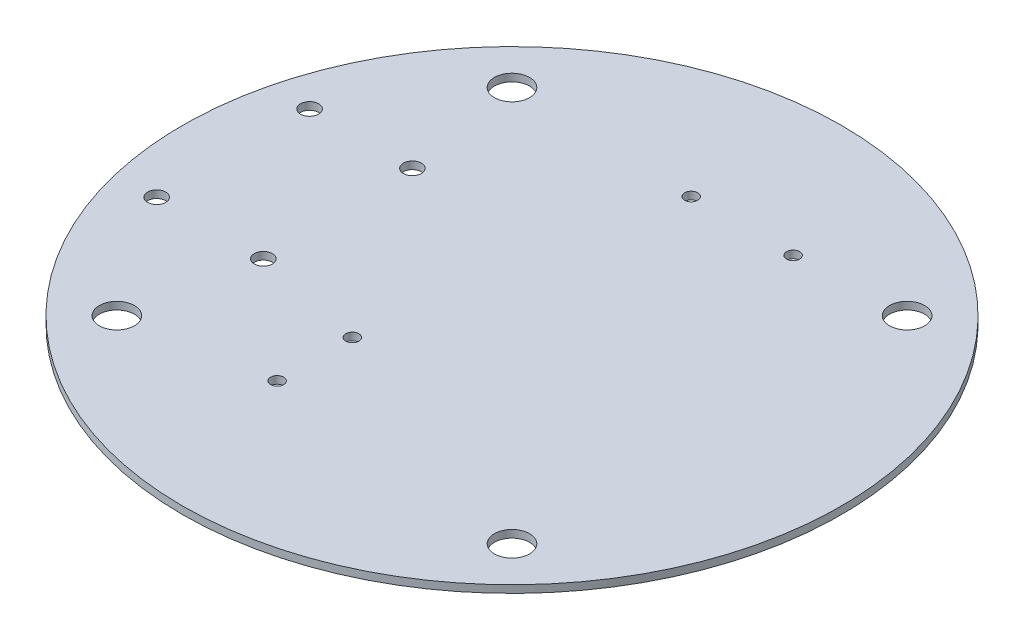
SolidWorks part; units mm, degrees
ref_plane "Front Plane" through (0, 0, 0) normal (0, 0, 1) x (1, 0, 0)
ref_plane "Top Plane" through (0, 0, 0) normal (0, 1, 0) x (1, 0, 0)
ref_plane "Right Plane" through (0, 0, 0) normal (1, 0, 0) x (0, 0, -1)
sketch "Sketch1" plane through (0, 0, 0) normal (0, 1, 0) x (1, 0, 0)
  circle A0 centre (0, 0) radius 65.7
  dimension "PCBdiam" = 131.4
extrude "Boss-Extrude1" add sketch "Sketch1" along normal blind 1.5
hole_wizard "M6 Clearance Hole1" positions "Sketch2" profile "Sketch4" hole size "M6" standard "ANSI Metric" end condition through all
sketch "Sketch2" plane through (0, 1.5, 0) normal (0, 1, 0) x (1, 0, 0)
  line L0 (0, 0) -> (-28.5457, 28.5457) construction
  line L1 (-39.3858, -39.3858) -> (0, 0) construction
  line L3 (0, 0) -> (-73.422, 0) construction
  circle A0 centre (0, 0) radius 65.7 construction
  ellipse E2 centre (-116.4291, -176.9435) end of major axis (-117.7556, -176.0714) minor radius 1.3748
  ellipse E3 centre (-116.4291, -176.9435) end of major axis (-115.1026, -177.8157) minor radius 1.3748
  point P7 (-39.3858, -39.3858)
  dimension "D1" = 0
  dimension "holeRadius" = 55.7
  dimension "D2" = 45
sketch "Sketch4" plane through (-39.3858, 1.5, 39.3858) normal (1, 0, 0) x (0, 0, 1)
  line L0 (0, 0) -> (0, 1.5)
  line L1 (0, 1.5) -> (3.5, 1.5)
  line L2 (3.5, 1.5) -> (3.5, 0)
  line L5 (3.5, 0) -> (0, 0)
  line L11 (0, -6.35) -> (0, 107.95) construction
  dimension "Thru Hole Dia." = 7
  dimension "Thru Hole Depth" = 1.5
pattern_circular "CirPattern1" count 4 over 360 about axis through (0, 1.5, 0) along (0, -1, 0) of "M6 Clearance Hole1"
sketch "Teensy Outline" plane through (0, 1.5, 0) normal (0, 1, 0) x (1, 0, 0)
  line L1 (-29.654, 50.7) -> (-12, 50.7)
  line L2 (-29.654, 50.7) -> (-29.654, -7.72)
  line L3 (-29.654, -7.72) -> (-12, -7.72)
  line L4 (-12, 50.7) -> (-12, -7.72)
  circle A1 centre (0, 0) radius 65.7 construction
  dimension "D1" = 17.654
  dimension "D2" = 58.42
  dimension "D3" = 12
  dimension "D4" = 15
sketch "BMP390 Outline" plane through (0, 1.5, 0) normal (0, 1, 0) x (1, 0, 0)
  line L0 (17.61, 54.7) -> (-5.25, 54.7) construction
  line L2 (20.15, 56.04) -> (-5.25, 56.04)
  line L3 (-5.25, 56.04) -> (-5.25, 38.26)
  line L4 (20.15, 38.26) -> (-5.25, 38.26)
  line L6 (20.15, 56.04) -> (20.15, 38.26)
  line L7 (17.61, 54.7) -> (17.61, 38.26) construction
  line L8 (-29.654, 50.7) -> (-12, 50.7) construction
  line L9 (-12, 50.7) -> (-12, -7.72) construction
  dimension "D1" = 17.78
  dimension "D2" = 25.4
  dimension "D3" = 1.34
  dimension "D4" = 4
  dimension "D5" = 6.75
  dimension "D6" = 5.08
sketch "NEO-6M Outline" plane through (0, 1.5, 0) normal (0, 1, 0) x (1, 0, 0)
  line L0 (-50.84, 17.78) -> (-50.84, 15.24) construction
  line L1 (-58.34, 17.78) -> (-32, 17.78)
  line L2 (-58.34, 17.78) -> (-58.34, -17.78)
  line L3 (-58.34, -17.78) -> (-32, -17.78)
  line L4 (-32, 17.78) -> (-32, -17.78)
  line L5 (-50.84, 15.24) -> (-39.5, 15.24) construction
  line L6 (-39.5, 15.24) -> (-39.5, 17.78) construction
  point P4 (-32, 0)
  point P9 (-45.17, 15.24)
  point P11 (-45.17, 17.78)
  dimension "D1" = 26.34
  dimension "D2" = 35.56
  dimension "D3" = 32
  dimension "D4" = 7.5
  dimension "D5" = 2.54
sketch "Xbee outline" plane through (0, 1.5, 0) normal (0, 1, 0) x (1, 0, 0)
  line L0 (9, 6.5) -> (26, 6.5) construction
  line L1 (26, 1.875) -> (26, 11.125)
  line L2 (26, 11.125) -> (19.5, 18.75)
  line L3 (19.5, 18.75) -> (-7, 18.75)
  line L4 (-7, 18.75) -> (-7, -5.75)
  line L5 (19.5, -5.75) -> (-7, -5.75)
  line L6 (26, 1.875) -> (19.5, -5.75)
  line L7 (0, 0) -> (72.9219, 0) construction
  line L9 (-12, 50.7) -> (-12, -7.72) construction
  line L10 (61, 12) -> (26, 12) construction
  line L11 (61, 12) -> (61, 1) construction
  line L12 (61, 1) -> (26, 1) construction
  line L13 (26, 12) -> (26, 1) construction
  point P7 (-7, 6.5)
  point P11 (26, 6.5)
  dimension "D1" = 24.5
  dimension "D2" = 33
  dimension "D3" = 26.5
  dimension "D4" = 9.25
  dimension "D5" = 16
  dimension "D6" = 35
  dimension "D7" = 11
  dimension "D8" = 6.5
  dimension "D9" = 5
sketch "Accel, gyro outline" plane through (0, 1.5, 0) normal (0, 1, 0) x (1, 0, 0)
  line L0 (47.32, 31.44) -> (27, 31.44) construction
  line L1 (52.4, 32.78) -> (27, 32.78)
  line L2 (27, 32.78) -> (27, 15)
  line L3 (52.4, 15) -> (27, 15)
  line L4 (52.4, 32.78) -> (52.4, 15)
  line L5 (47.32, 31.44) -> (47.32, 16.34) construction
  line L6 (27, 23.89) -> (52.4, 23.89) construction
  line L7 (47.32, 16.34) -> (27, 16.34) construction
  dimension "D1" = 17.78
  dimension "D2" = 25.4
  dimension "D3" = 1.34
  dimension "D4" = 5.08
  dimension "D5" = 15
  dimension "D6" = 27
sketch "Sketch17" plane through (0, 1.5, 0) normal (0, 1, 0) x (1, 0, 0)
  line L0 (-29.654, -23.3858) -> (-36.154, -23.3858) construction
  line L1 (-29.654, -17.3858) -> (-9.654, -17.3858)
  line L2 (-29.654, -17.3858) -> (-29.654, -37.3858)
  line L3 (-29.654, -37.3858) -> (-9.654, -37.3858)
  line L4 (-9.654, -17.3858) -> (-9.654, -37.3858)
  line L5 (-36.154, -23.3858) -> (-36.154, -31.3858) construction
  line L6 (-36.154, -31.3858) -> (-29.654, -31.3858) construction
  line L7 (-29.654, 50.7) -> (-29.654, -7.72) construction
  circle A0 centre (-39.3858, -39.3858) radius 3.5 construction
  point P8 (-36.154, -27.3858)
  point P9 (-29.654, -27.3858)
  dimension "D1" = 20
  dimension "D2" = 20
  dimension "D3" = 6.5
  dimension "D4" = 8
  dimension "D5" = 0
  dimension "D6" = 2
hole_wizard "M2 Clearance Hole1" positions "Sketch20" profile "Sketch19" hole size "M2" standard "ANSI Metric" end condition through all
sketch "Sketch20" plane through (0, 1.5, 0) normal (0, 1, 0) x (1, 0, 0)
  circle A0 centre (-2.71, 38.43) radius 1.2493 construction
  circle A1 centre (17.61, 38.43) radius 1.2493 construction
  circle A2 centre (-12.154, -19.6737) radius 1.25 construction
  circle A3 centre (-12.154, -19.6737) radius 1.25 construction
  circle A4 centre (-12.154, -34.6737) radius 1.25 construction
  circle A5 centre (-12.154, -34.6737) radius 1.25 construction
  point P1 (-2.71, 38.43)
  point P7 (17.61, 38.43)
  point P13 (-12.154, -19.6737)
  point P16 (-12.154, -34.6737)
sketch "Sketch19" plane through (-2.71, 1.5, -38.43) normal (1, 0, 0) x (0, 0, 1)
  line L0 (0, 0) -> (0, 1.5)
  line L1 (0, 1.5) -> (1.3, 1.5)
  line L2 (1.3, 1.5) -> (1.3, 0)
  line L5 (1.3, 0) -> (0, 0)
  line L11 (0, -6.35) -> (0, 107.95) construction
  dimension "Thru Hole Dia." = 2.6
  dimension "Thru Hole Depth" = 1.5
hole_wizard "M3 Clearance Hole2" positions "Sketch21" profile "Sketch22" hole size "M3" standard "ANSI Metric" end condition through all
sketch "Sketch21" plane through (0, 1.5, 0) normal (0, 1, 0) x (1, 0, 0)
  point P0 (-55.8645, 15.5117)
  point P3 (-55.8645, -14.9683)
  point P6 (-34.6045, -14.9683)
  point P9 (-35.3665, 15.5117)
sketch "Sketch22" plane through (-55.8645, 1.5, -15.5117) normal (1, 0, 0) x (0, 0, 1)
  line L0 (0, 0) -> (0, 1.5)
  line L1 (0, 1.5) -> (1.8, 1.5)
  line L2 (1.8, 1.5) -> (1.8, 0)
  line L5 (1.8, 0) -> (0, 0)
  line L11 (0, -6.35) -> (0, 107.95) construction
  dimension "Thru Hole Dia." = 3.6
  dimension "Thru Hole Depth" = 1.5
